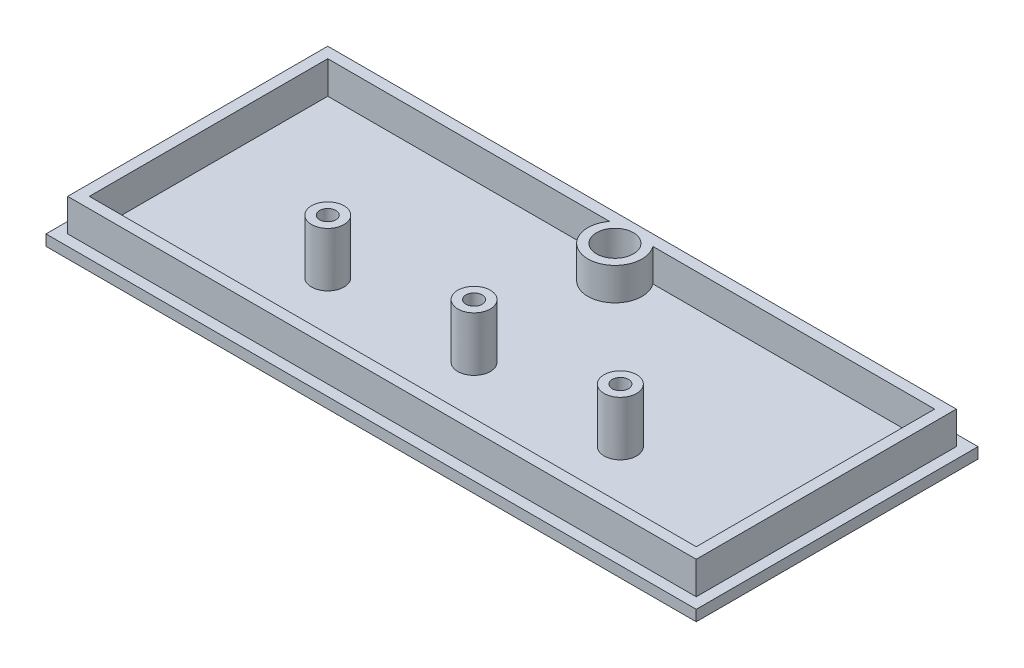
SolidWorks part; units mm, degrees
ref_plane "Front" through (0, 0, 0) normal (0, 0, 1) x (1, 0, 0)
ref_plane "Top" through (0, 0, 0) normal (0, 1, 0) x (1, 0, 0)
ref_plane "Right" through (0, 0, 0) normal (1, 0, 0) x (0, 0, -1)
sketch "Sketch1" plane through (0, 0, 0) normal (0, 1, 0) x (1, 0, 0)
  line L1 (0, 0) -> (60, 0)
  line L2 (0, 0) -> (0, 26)
  line L3 (0, 26) -> (60, 26)
  line L4 (60, 0) -> (60, 26)
  dimension "D1" = 26
  dimension "D2" = 60
extrude "Boss-Extrude1" add sketch "Sketch1" along normal blind 1
sketch "Sketch2" plane through (0, 1, 0) normal (0, 1, 0) x (1, 0, 0)
  line L0 (60, 26) -> (0, 26) construction
  line L1 (1, 25) -> (59, 25)
  line L2 (1, 25) -> (1, 1)
  line L3 (1, 1) -> (59, 1)
  line L4 (59, 25) -> (59, 1)
  line L5 (0, 26) -> (0, 0) construction
  line L6 (0, 0) -> (60, 0) construction
  line L7 (60, 0) -> (60, 26) construction
  line L9 (2, 24) -> (58, 24)
  line L10 (2, 24) -> (2, 2)
  line L11 (2, 2) -> (58, 2)
  line L12 (58, 24) -> (58, 2)
  dimension "D1" = 1
  dimension "D2" = 1
  dimension "D3" = 1
  dimension "D4" = 1
  dimension "D5" = 1
  dimension "D6" = 1
  dimension "D7" = 1
  dimension "D8" = 1
extrude "Boss-Extrude2" add sketch "Sketch2" along normal blind 3
sketch "Sketch3" plane through (0, 1, 0) normal (0, 1, 0) x (1, 0, 0)
  line L0 (2, 24) -> (2, 2) construction
  line L2 (2, 2) -> (58, 2) construction
  circle A0 centre (16.5, 9.5) radius 1.5
  circle A1 centre (30, 9.5) radius 1.5
  circle A2 centre (43.5, 9.5) radius 1.5
  circle A3 centre (16.5, 9.5) radius 0.75
  circle A4 centre (30, 9.5) radius 0.75
  circle A5 centre (43.5, 9.5) radius 0.75
  dimension "D1" = 3
  dimension "D2" = 3
  dimension "D3" = 3
  dimension "D8" = 1.5
  dimension "D9" = 1.5
  dimension "D10" = 1.5
  dimension "D4" = 14.5
  dimension "D5" = 13.5
  dimension "D6" = 13.5
  dimension "D7" = 7.5
extrude "Boss-Extrude3" add sketch "Sketch3" along normal blind 5
sketch "Sketch6" plane through (0, 1, 0) normal (0, 1, 0) x (1, 0, 0)
  line L0 (60, 26) -> (0, 26) construction
  line L1 (0, 26) -> (0, 0) construction
  circle A0 centre (30, 22.5) radius 2.5
  dimension "D3" = 5
  dimension "D1" = 3.5
  dimension "D2" = 30
extrude "Boss-Extrude4" add sketch "Sketch6" along normal blind 3
hole_wizard "CSK for M3 Flat Head Machine Screw1" positions "Sketch5" profile "Sketch4" countersink size "M3" standard "ANSI Metric" end condition through all
sketch "Sketch5" plane through (0, 0, 0) normal (0, -1, 0) x (-1, 0, 0)
  line L0 (-60, 26) -> (0, 26) construction
  line L1 (0, 26) -> (0, 0) construction
  point P0 (-30, 22.5)
  dimension "D1" = 3.5
  dimension "D2" = 30
sketch "Sketch4" plane through (30, 0, -22.5) normal (1, 0, 0) x (0, 0, -1)
  line L0 (0, 0) -> (0, 6)
  line L1 (0, 6) -> (1.7, 6)
  line L2 (1.7, 6) -> (1.7, 1.45)
  line L3 (1.7, 1.45) -> (3.15, 0)
  line L5 (3.15, 0) -> (0, 0)
  line L6 (-1.7, 1.45) -> (-3.15, 0) construction
  line L11 (0, -6.35) -> (0, 107.95) construction
  dimension "Thru Hole Dia." = 3.4
  dimension "Thru Hole Depth" = 6
  dimension "Near C'Sink Dia." = 6.3
  dimension "Near C'Sink Angle" = 90
